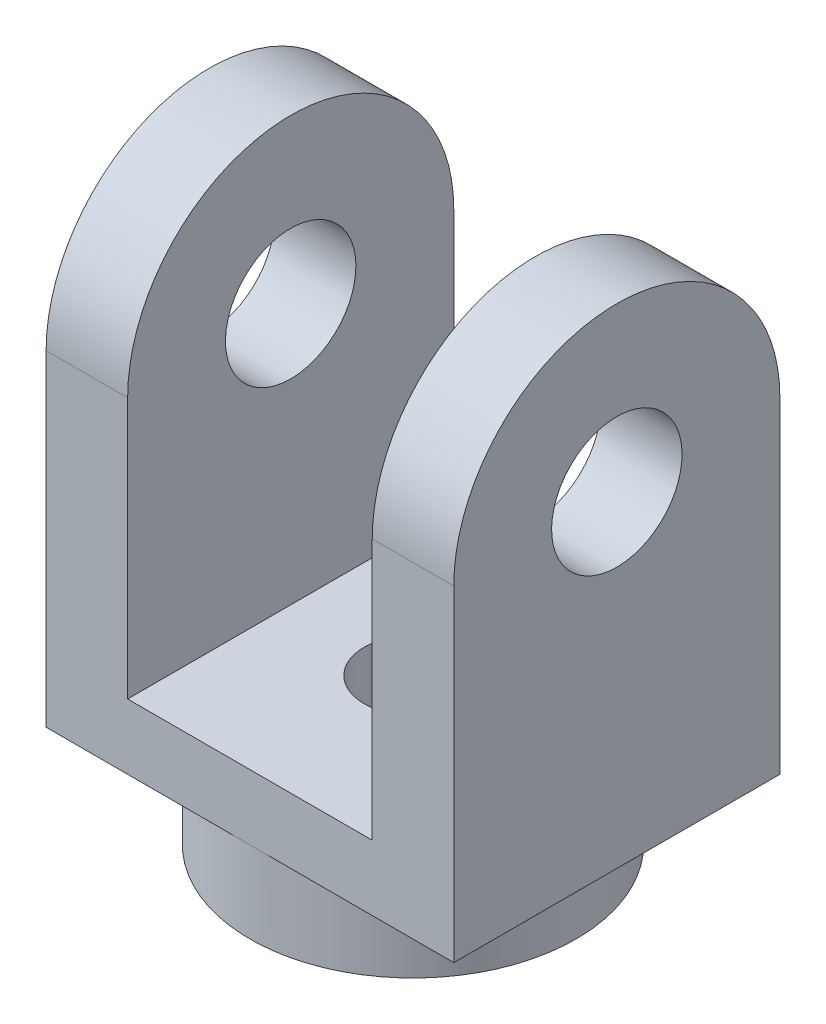
SolidWorks part; units mm, degrees
other "Markup1"
sketch "Sketch5" plane through (-62.5, 175, -50) normal (-0.996, 0.0856, -0.0239) x (-0.0052, 0.2118, 0.9773)
ref_plane "Front Plane" through (0, 0, 0) normal (0, 0, 1) x (1, 0, 0)
ref_plane "Top Plane" through (0, 0, 0) normal (0, 1, 0) x (1, 0, 0)
ref_plane "Right Plane" through (0, 0, 0) normal (1, 0, 0) x (0, 0, -1)
sketch "Sketch1" plane through (0, 0, 0) normal (0, 0, 1) x (1, 0, 0)
  line L0 (-62.5, 125) -> (-62.5, 25)
  line L1 (-62.5, 25) -> (62.5, 25)
  line L2 (62.5, 25) -> (62.5, 125)
  line L3 (62.5, 125) -> (37.5, 125)
  line L4 (37.5, 125) -> (37.5, 45)
  line L5 (37.5, 45) -> (-37.5, 45)
  line L6 (-37.5, 45) -> (-37.5, 125)
  line L7 (-37.5, 125) -> (-62.5, 125)
  line L8 (0, 25) -> (0, 62.2726) construction
  point P11 (0, 25)
  point P12 (0, 25)
  point P13 (0, 0)
  point P14 (0, 44.3243)
  point P15 (0, 0)
  point P16 (0, 62.2726)
  dimension "D1" = 25
  dimension "D2" = 125
  dimension "D3" = 25
  dimension "D4" = 25
  dimension "D5" = 100
  dimension "D6" = 20
extrude "Boss-Extrude1" add sketch "Sketch1" along normal mid plane 100
sketch "Sketch3" plane through (-62.5, 0, 0) normal (-1, 0, 0) x (0, 0, 1)
  circle A1 centre (0, 125) radius 50
extrude "Boss-Extrude5" add sketch "Sketch3" against normal blind 25
sketch "Sketch4" plane through (-62.5, 0, 0) normal (-1, 0, 0) x (0, 0, 1)
  line L0 (50, 25) -> (-50, 25) construction
  circle A0 centre (0, 125) radius 20
  point P2 (0, 0)
  point P5 (0, 125)
  dimension "D1" = 40
  dimension "D2" = 100
  dimension "D3" = 50
extrude "Cut-Extrude1" cut sketch "Sketch4" against normal blind 25
mirror "Mirror1" about plane through (0, 0, 0) normal (1, 0, 0) of "Cut-Extrude1", "Boss-Extrude5"
ref_axis "Axis1" through (0, 0, 0) along (0, 1, 0)
sketch "Sketch8" plane through (0, 45, 0) normal (0, 1, 0) x (1, 0, 0)
  circle A0 centre (0, 0) radius 15
  dimension "D1" = 30
extrude "Cut-Extrude2" cut sketch "Sketch8" against normal through all
sketch "Sketch9" plane through (0, 25, 0) normal (0, -1, 0) x (1, 0, 0)
  circle A0 centre (0, 0) radius 37.5
  circle A1 centre (0, 0) radius 50
  dimension "D1" = 75
  dimension "D2" = 100
extrude "Boss-Extrude6" add sketch "Sketch9" along normal blind 25
